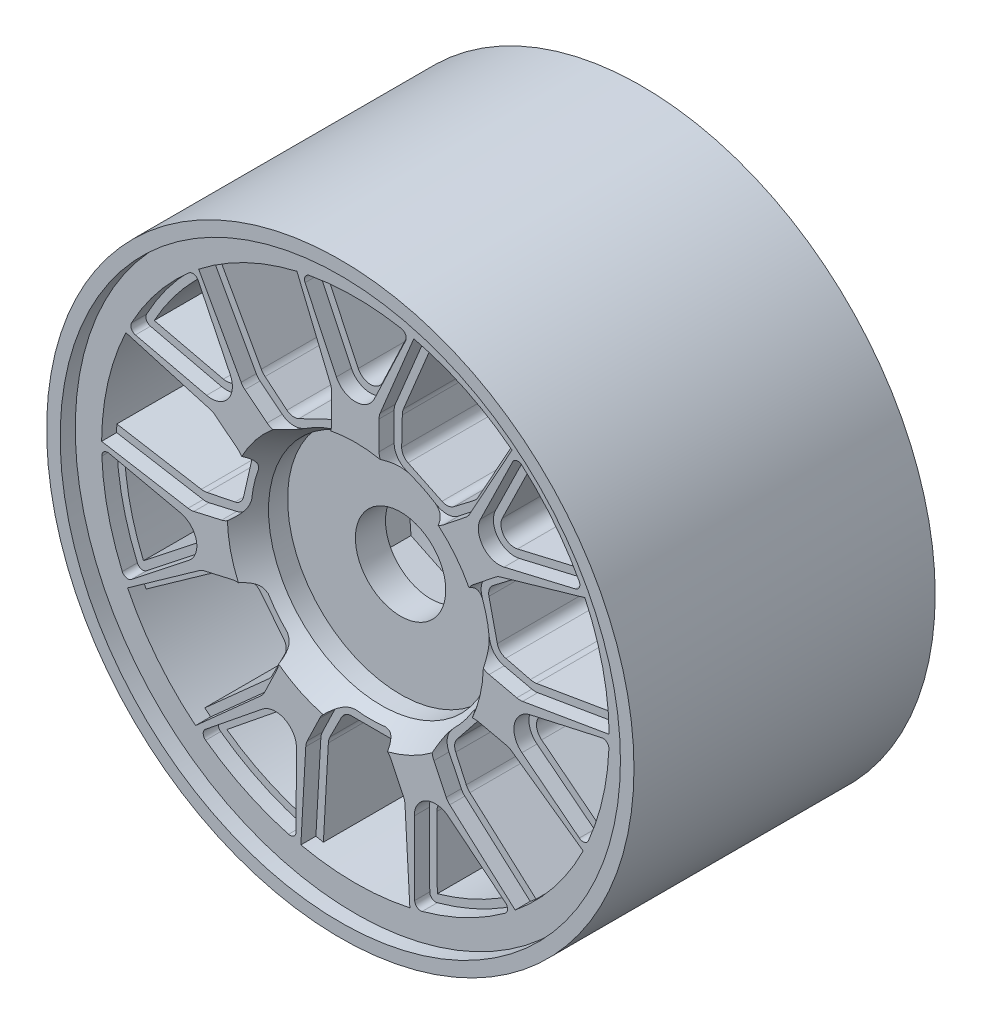
SolidWorks part; units mm, degrees
material "ABS"
ref_plane "Front Plane" through (0, 0, 0) normal (0, 0, 1) x (1, 0, 0)
ref_plane "Top Plane" through (0, 0, 0) normal (0, 1, 0) x (1, 0, 0)
ref_plane "Right Plane" through (0, 0, 0) normal (1, 0, 0) x (0, 0, -1)
sketch "Sketch1" plane through (0, 0, 0) normal (0, 0, 1) x (1, 0, 0)
  circle A0 centre (0, 0) radius 39
  dimension "D1" = 78
extrude "Boss-Extrude1" add sketch "Sketch1" along normal blind 40
sketch "Sketch2" plane through (0, 0, 0) normal (0, 0, -1) x (-1, 0, 0)
  circle A0 centre (0, 0) radius 38
  circle A1 centre (0, 0) radius 39 construction
  dimension "D1" = 1
extrude "Cut-Extrude1" cut sketch "Sketch2" against normal blind 19
sketch "Sketch3" plane through (0, 0, 40) normal (0, 0, 1) x (1, 0, 0)
  circle A0 centre (0, 0) radius 37.2
  circle A1 centre (0, 0) radius 39 construction
  dimension "D1" = 1.8
extrude "Cut-Extrude2" cut sketch "Sketch3" against normal blind 2
sketch "Sketch5" plane through (0, 0, 38) normal (0, 0, 1) x (1, 0, 0)
  circle A0 centre (0, 0) radius 6
  dimension "D1" = 12
extrude "Cut-Extrude3" cut sketch "Sketch5" against normal through all
sketch "Sketch6" plane through (0, 0, 38) normal (0, 0, 1) x (1, 0, 0)
  circle A0 centre (0, 0) radius 33.7
  circle A1 centre (0, 0) radius 37.2 construction
  dimension "D1" = 3.5
sketch "Sketch7" plane through (0, 0, 38) normal (0, 0, 1) x (1, 0, 0)
  line L0 (0, 42.1096) -> (0, -43.6902) construction
  line L1 (-45.1954, 0) -> (51.367, 0) construction
  line L2 (-3.15, 14.6655) -> (-3.15, 21.2677)
  line L3 (-3.15, 21.6655) -> (3.15, 21.6655)
  line L4 (3.15, 21.2677) -> (3.15, 14.6655)
  line L5 (-6.6789, 32.0306) -> (-2.5217, 23.2608)
  line L6 (2.5217, 23.2608) -> (6.6789, 32.0306)
  line L7 (3.3022, 22.0331) -> (7.7598, 32.7945)
  line L8 (-3.3022, 22.0331) -> (-7.7598, 32.7945)
  line L9 (1.618, 23.6891) -> (5.656, 32.2071)
  line L10 (-5.656, 32.2071) -> (-1.618, 23.6891)
  line L11 (20.8783, 25.1925) -> (16.6138, 16.4744)
  line L12 (21.6541, 24.5028) -> (17.5121, 16.035)
  line L13 (19.2851, 11.1556) -> (30.4779, 14.3802)
  line L14 (19.5297, 13.5049) -> (28.707, 15.6588)
  line L15 (19.7582, 12.5314) -> (29.2068, 14.749)
  line L16 (15.1672, 16.3192) -> (20.8016, 26.5138)
  line L17 (14.9748, 15.971) -> (18.9028, 11.0455)
  line L18 (9.502, 11.6066) -> (14.6638, 15.723)
  line L19 (18.5917, 10.7974) -> (13.43, 6.681)
  line L20 (32.7137, -0.616) -> (23.2387, -2.7176)
  line L21 (32.6582, -1.6526) -> (23.4552, -3.6939)
  line L22 (20.7458, -8.1223) -> (30.2455, -14.8627)
  line L23 (22.7352, -6.8488) -> (30.1411, -12.6809)
  line L24 (22.1165, -7.6344) -> (29.7413, -13.639)
  line L25 (22.2155, -1.6834) -> (33.6989, 0.2677)
  line L26 (21.8233, -1.75) -> (20.4214, -7.8921)
  line L27 (14.9988, -0.1924) -> (21.4354, -1.6615)
  line L28 (20.0335, -7.8035) -> (13.5969, -6.3344)
  line L29 (19.9151, -25.9607) -> (12.3644, -19.8631)
  line L30 (19.07, -26.5636) -> (11.7361, -20.6411)
  line L31 (6.5846, -21.2839) -> (7.2377, -32.9136)
  line L32 (8.8205, -22.0452) -> (8.8783, -31.4717)
  line L33 (7.8205, -22.0513) -> (7.88, -31.7564)
  line L34 (12.535, -18.4183) -> (21.2203, -26.18)
  line L35 (12.2384, -18.1532) -> (6.5623, -20.8867)
  line L36 (9.2012, -11.8464) -> (12.0658, -17.7948)
  line L37 (6.3897, -20.5283) -> (3.5251, -14.5799)
  line L38 (-7.88, -31.7564) -> (-7.8205, -22.0513)
  line L39 (-8.8783, -31.4717) -> (-8.8205, -22.0452)
  line L40 (-12.535, -18.4183) -> (-21.2203, -26.18)
  line L41 (-11.7361, -20.6411) -> (-19.07, -26.5636)
  line L42 (-12.3644, -19.8631) -> (-19.9151, -25.9607)
  line L43 (-6.5846, -21.2839) -> (-7.2377, -32.9136)
  line L44 (-6.5623, -20.8867) -> (-12.2384, -18.1532)
  line L45 (-3.5251, -14.5799) -> (-6.3897, -20.5283)
  line L46 (-12.0658, -17.7948) -> (-9.2012, -11.8464)
  line L47 (-29.7413, -13.639) -> (-22.1165, -7.6344)
  line L48 (-30.1411, -12.6809) -> (-22.7352, -6.8488)
  line L49 (-22.2155, -1.6834) -> (-33.6989, 0.2677)
  line L50 (-23.4552, -3.6939) -> (-32.6582, -1.6526)
  line L51 (-23.2387, -2.7176) -> (-32.7137, -0.616)
  line L52 (-20.7458, -8.1223) -> (-30.2455, -14.8627)
  line L53 (-20.4214, -7.8921) -> (-21.8233, -1.75)
  line L54 (-13.5969, -6.3344) -> (-20.0335, -7.8035)
  line L55 (-21.4354, -1.6615) -> (-14.9988, -0.1924)
  line L56 (-29.2068, 14.749) -> (-19.7582, 12.5314)
  line L57 (-28.707, 15.6588) -> (-19.5297, 13.5049)
  line L58 (-15.1672, 16.3192) -> (-20.8016, 26.5138)
  line L59 (-17.5121, 16.035) -> (-21.6541, 24.5028)
  line L60 (-16.6138, 16.4744) -> (-20.8783, 25.1925)
  line L61 (-19.2851, 11.1556) -> (-30.4779, 14.3802)
  line L62 (-18.9028, 11.0455) -> (-14.9748, 15.971)
  line L63 (-13.43, 6.681) -> (-18.5917, 10.7974)
  line L64 (-14.6638, 15.723) -> (-9.502, 11.6066)
  line L65 (4.5653, 15.2418) -> (9.0701, 13.0724)
  line L67 (3.15, 14.6655) -> (9.502, 11.6066) construction
  line L69 (6.326, 13.136) -> (7.7598, 16.1133) construction
  line L70 (4.9992, 16.1428) -> (9.504, 13.9734)
  line L71 (8.7397, 32.547) -> (4.3846, 22.0331)
  line L72 (4.2324, 21.2677) -> (4.15, 17.4943)
  line L73 (19.9972, 27.1257) -> (14.2999, 16.8172)
  line L74 (13.7639, 16.1956) -> (11.0901, 14.1521)
  line L75 (14.9748, 15.971) -> (13.7119, 17.5546) construction
  line L76 (14.763, 5.9338) -> (15.8756, 1.0592)
  line L77 (15.7379, 6.1564) -> (16.8505, 1.2817)
  line L78 (19.2666, 9.9512) -> (16.265, 7.6629)
  line L79 (30.8954, 13.4598) -> (19.9599, 10.3093)
  line L80 (19.2851, 11.1556) -> (30.4779, 14.3802)
  line L81 (18.5917, 10.7974) -> (13.43, 6.681)
  line L82 (21.2439, -0.6633) -> (17.9791, 0.1531)
  line L83 (14.9988, -0.1924) -> (21.4354, -1.6615)
  line L84 (33.6758, 1.2781) -> (22.0641, -0.6948)
  line L85 (22.2155, -1.6834) -> (33.6989, 0.2677)
  line L86 (13.43, 6.681) -> (14.9988, -0.1924) construction
  line L87 (14.2144, 3.2443) -> (17.436, 3.9797) construction
  line L88 (13.8438, -7.8425) -> (10.7264, -11.7516)
  line L89 (14.6256, -8.4659) -> (11.5082, -12.3751)
  line L90 (19.7927, -8.8588) -> (16.1322, -7.9388)
  line L91 (29.7862, -15.7629) -> (20.505, -9.1775)
  line L92 (20.7458, -8.1223) -> (30.2455, -14.8627)
  line L93 (20.0335, -7.8035) -> (13.5969, -6.3344)
  line L94 (12.7268, -17.0227) -> (11.3295, -13.9612)
  line L95 (9.2012, -11.8464) -> (12.0658, -17.7948)
  line L96 (21.9958, -25.5319) -> (13.2136, -17.6836)
  line L97 (12.535, -18.4183) -> (21.2203, -26.18)
  line L98 (13.5969, -6.3344) -> (9.2012, -11.8464) construction
  line L99 (11.399, -9.0904) -> (13.9826, -11.1507) construction
  line L100 (2.5, -15.7132) -> (-2.5, -15.7132)
  line L101 (2.5, -16.7132) -> (-2.5, -16.7132)
  line L102 (5.4145, -20.9979) -> (3.8515, -17.5624)
  line L103 (6.2475, -33.1158) -> (5.6094, -21.7535)
  line L104 (6.5846, -21.2839) -> (7.2377, -32.9136)
  line L105 (6.3897, -20.5283) -> (3.5251, -14.5799)
  line L106 (-5.3739, -20.5637) -> (-3.8515, -17.5624)
  line L107 (-3.5251, -14.5799) -> (-6.3897, -20.5283)
  line L108 (-6.2475, -33.1158) -> (-5.5871, -21.3563)
  line L109 (-6.5846, -21.2839) -> (-7.2377, -32.9136)
  line L110 (3.5251, -14.5799) -> (-3.5251, -14.5799) construction
  line L111 (0, -14.5799) -> (0, -17.8844) construction
  line L112 (-10.7264, -11.7516) -> (-13.8438, -7.8425)
  line L113 (-11.5082, -12.3751) -> (-14.6256, -8.4659)
  line L114 (-13.041, -17.3252) -> (-11.3295, -13.9612)
  line L115 (-21.9958, -25.5319) -> (-13.5102, -17.9487)
  line L116 (-12.535, -18.4183) -> (-21.2203, -26.18)
  line L117 (-12.0658, -17.7948) -> (-9.2012, -11.8464)
  line L118 (-19.4279, -8.6198) -> (-16.1322, -7.9388)
  line L119 (-13.5969, -6.3344) -> (-20.0335, -7.8035)
  line L120 (-29.7862, -15.7629) -> (-20.1805, -8.9473)
  line L121 (-20.7458, -8.1223) -> (-30.2455, -14.8627)
  line L122 (-9.2012, -11.8464) -> (-13.5969, -6.3344) construction
  line L123 (-11.399, -9.0904) -> (-13.9826, -11.1507) construction
  line L124 (-15.8756, 1.0592) -> (-14.763, 5.9338)
  line L125 (-16.8505, 1.2817) -> (-15.7379, 6.1564)
  line L126 (-21.6763, -0.6062) -> (-17.9791, 0.1531)
  line L127 (-33.6758, 1.2781) -> (-22.4563, -0.6281)
  line L128 (-22.2155, -1.6834) -> (-33.6989, 0.2677)
  line L129 (-21.4354, -1.6615) -> (-14.9988, -0.1924)
  line L130 (-18.8523, 9.815) -> (-16.265, 7.6629)
  line L131 (-13.43, 6.681) -> (-18.5917, 10.7974)
  line L132 (-30.8954, 13.4598) -> (-19.5776, 10.1992)
  line L133 (-19.2851, 11.1556) -> (-30.4779, 14.3802)
  line L134 (-14.9988, -0.1924) -> (-13.43, 6.681) construction
  line L135 (-14.2144, 3.2443) -> (-17.436, 3.9797) construction
  line L136 (-9.0701, 13.0724) -> (-4.5653, 15.2418)
  line L137 (-9.504, 13.9734) -> (-4.9992, 16.1428)
  line L138 (-13.9889, 16.5692) -> (-11.0901, 14.1521)
  line L139 (-19.9972, 27.1257) -> (-14.4924, 17.1654)
  line L140 (-15.1672, 16.3192) -> (-20.8016, 26.5138)
  line L141 (-14.6638, 15.723) -> (-9.502, 11.6066)
  line L142 (-4.0806, 20.8589) -> (-4.15, 17.4943)
  line L143 (-3.15, 14.6655) -> (-3.15, 21.2677)
  line L144 (-8.7397, 32.547) -> (-4.2324, 21.6655)
  line L145 (-3.3022, 22.0331) -> (-7.7598, 32.7945)
  line L146 (-9.502, 11.6066) -> (-3.15, 14.6655) construction
  line L147 (-6.326, 13.136) -> (-7.7598, 16.1133) construction
  circle A0 centre (0, 0) radius 15
  circle A1 centre (0, 0) radius 33.7 construction
  arc A2 (-6.1106, 33.1414) -> (6.1106, 33.1414) centre (0, 0) cw
  arc A3 (-6.1106, 33.1414) -> (-6.6789, 32.0306) centre (-5.968, 32.3676) ccw
  arc A4 (6.1106, 33.1414) -> (6.6789, 32.0306) centre (5.968, 32.3676) cw
  arc A5 (-2.5217, 23.2608) -> (2.5217, 23.2608) centre (0, 24.4562) ccw
  arc A6 (-33.7, 0) -> (33.7, 0) centre (0, 0) ccw
  arc A7 (7.7598, 32.7945) -> (-7.7598, 32.7945) centre (0, 0) ccw
  arc A8 (-5.656, 32.2071) -> (5.656, 32.2071) centre (0, 0) cw
  arc A9 (5.656, 32.2071) -> (5.656, 32.2071) centre (5.656, 32.2071) cw
  arc A10 (-1.618, 23.6891) -> (1.618, 23.6891) centre (0, 24.4562) ccw
  arc A11 (-5.656, 32.2071) -> (-5.656, 32.2071) centre (-5.656, 32.2071) ccw
  arc A12 (21.6541, 24.5028) -> (28.707, 15.6588) centre (0, 0) cw
  arc A13 (22.101, 25.4408) -> (29.7209, 15.8858) centre (0, 0) cw
  arc A14 (22.101, 25.4408) -> (20.8783, 25.1925) centre (21.5851, 24.8468) ccw
  arc A15 (30.4779, 14.3802) -> (20.8016, 26.5138) centre (0, 0) ccw
  arc A16 (29.7209, 15.8858) -> (29.2068, 14.749) centre (29.027, 15.5149) cw
  arc A17 (16.6138, 16.4744) -> (19.7582, 12.5314) centre (19.1206, 15.2482) ccw
  arc A18 (17.5121, 16.035) -> (19.5297, 13.5049) centre (19.1206, 15.2482) ccw
  arc A19 (32.6582, -1.6526) -> (30.1411, -12.6809) centre (0, 0) cw
  arc A20 (33.6702, -1.4172) -> (30.9507, -13.3321) centre (0, 0) cw
  arc A21 (33.6702, -1.4172) -> (32.7137, -0.616) centre (32.8841, -1.3841) ccw
  arc A22 (30.2455, -14.8627) -> (33.6989, 0.2677) centre (0, 0) ccw
  arc A23 (30.9507, -13.3321) -> (29.7413, -13.639) centre (30.2281, -13.0208) cw
  arc A24 (23.2387, -2.7176) -> (22.1165, -7.6344) centre (23.843, -5.442) ccw
  arc A25 (23.4552, -3.6939) -> (22.7352, -6.8488) centre (23.843, -5.442) ccw
  arc A26 (19.07, -26.5636) -> (8.8783, -31.4717) centre (0, 0) cw
  arc A27 (19.885, -27.208) -> (8.874, -32.5106) centre (0, 0) cw
  arc A28 (19.885, -27.208) -> (19.9151, -25.9607) centre (19.4207, -26.5728) ccw
  arc A29 (7.2377, -32.9136) -> (21.2203, -26.18) centre (0, 0) ccw
  arc A30 (8.874, -32.5106) -> (7.88, -31.7564) centre (8.6668, -31.7516) cw
  arc A31 (12.3644, -19.8631) -> (7.8205, -22.0513) centre (10.6111, -22.0342) ccw
  arc A32 (11.7361, -20.6411) -> (8.8205, -22.0452) centre (10.6111, -22.0342) ccw
  arc A33 (-8.8783, -31.4717) -> (-19.07, -26.5636) centre (0, 0) cw
  arc A34 (-8.874, -32.5106) -> (-19.885, -27.208) centre (0, 0) cw
  arc A35 (-8.874, -32.5106) -> (-7.88, -31.7564) centre (-8.6668, -31.7516) ccw
  arc A36 (-21.2203, -26.18) -> (-7.2377, -32.9136) centre (0, 0) ccw
  arc A37 (-19.885, -27.208) -> (-19.9151, -25.9607) centre (-19.4207, -26.5728) cw
  arc A38 (-7.8205, -22.0513) -> (-12.3644, -19.8631) centre (-10.6111, -22.0342) ccw
  arc A39 (-8.8205, -22.0452) -> (-11.7361, -20.6411) centre (-10.6111, -22.0342) ccw
  arc A40 (-30.1411, -12.6809) -> (-32.6582, -1.6526) centre (0, 0) cw
  arc A41 (-30.9507, -13.3321) -> (-33.6702, -1.4172) centre (0, 0) cw
  arc A42 (-30.9507, -13.3321) -> (-29.7413, -13.639) centre (-30.2281, -13.0208) ccw
  arc A43 (-33.6989, 0.2677) -> (-30.2455, -14.8627) centre (0, 0) ccw
  arc A44 (-33.6702, -1.4172) -> (-32.7137, -0.616) centre (-32.8841, -1.3841) cw
  arc A45 (-22.1165, -7.6344) -> (-23.2387, -2.7176) centre (-23.843, -5.442) ccw
  arc A46 (-22.7352, -6.8488) -> (-23.4552, -3.6939) centre (-23.843, -5.442) ccw
  arc A47 (-28.707, 15.6588) -> (-21.6541, 24.5028) centre (0, 0) cw
  arc A48 (-29.7209, 15.8858) -> (-22.101, 25.4408) centre (0, 0) cw
  arc A49 (-29.7209, 15.8858) -> (-29.2068, 14.749) centre (-29.027, 15.5149) ccw
  arc A50 (-20.8016, 26.5138) -> (-30.4779, 14.3802) centre (0, 0) ccw
  arc A51 (-22.101, 25.4408) -> (-20.8783, 25.1925) centre (-21.5851, 24.8468) cw
  arc A52 (-19.7582, 12.5314) -> (-16.6138, 16.4744) centre (-19.1206, 15.2482) ccw
  arc A53 (-19.5297, 13.5049) -> (-17.5121, 16.035) centre (-19.1206, 15.2482) ccw
  arc A55 (3.15, 21.2677) -> (3.3022, 22.0331) centre (5.15, 21.2677) cw
  arc A56 (-3.15, 21.2677) -> (-3.3022, 22.0331) centre (-5.15, 21.2677) ccw
  arc A57 (-14.6638, 15.723) -> (-15.1672, 16.3192) centre (-13.4168, 17.2866) cw
  arc A58 (-18.5917, 10.7974) -> (-19.2851, 11.1556) centre (-19.8387, 9.2338) ccw
  arc A59 (-21.4354, -1.6615) -> (-22.2155, -1.6834) centre (-21.8805, 0.2884) cw
  arc A60 (-20.7458, -8.1223) -> (-20.0335, -7.8035) centre (-19.5885, -9.7534) cw
  arc A61 (-12.0658, -17.7948) -> (-12.535, -18.4183) centre (-13.8677, -16.927) cw
  arc A62 (-6.3897, -20.5283) -> (-6.5846, -21.2839) centre (-4.5877, -21.396) ccw
  arc A63 (12.0658, -17.7948) -> (12.535, -18.4183) centre (13.8677, -16.927) ccw
  arc A64 (6.3897, -20.5283) -> (6.5846, -21.2839) centre (4.5877, -21.396) cw
  arc A65 (20.0335, -7.8035) -> (20.7458, -8.1223) centre (19.5885, -9.7534) cw
  arc A66 (22.2155, -1.6834) -> (21.4354, -1.6615) centre (21.8805, 0.2884) cw
  arc A67 (19.2851, 11.1556) -> (18.5917, 10.7974) centre (19.8387, 9.2338) ccw
  arc A68 (15.1672, 16.3192) -> (14.6638, 15.723) centre (13.4168, 17.2866) cw
  arc A69 (4.5653, 15.2418) -> (3.15, 17.4943) centre (5.65, 17.4943) cw
  arc A70 (9.0701, 13.0724) -> (11.7136, 13.3703) centre (10.1548, 15.3248) ccw
  arc A71 (4.9992, 16.1428) -> (4.15, 17.4943) centre (5.65, 17.4943) cw
  arc A72 (9.504, 13.9734) -> (11.0901, 14.1521) centre (10.1548, 15.3248) ccw
  arc A73 (4.3846, 22.0331) -> (4.2324, 21.2677) centre (6.2324, 21.2677) ccw
  arc A74 (14.2999, 16.8172) -> (13.7639, 16.1956) centre (12.5495, 17.7847) cw
  arc A75 (8.7397, 32.547) -> (19.9972, 27.1257) centre (0, 0) cw
  arc A76 (14.763, 5.9338) -> (15.6416, 8.4447) centre (17.2003, 6.4901) cw
  arc A77 (15.7379, 6.1564) -> (16.265, 7.6629) centre (17.2003, 6.4901) cw
  arc A78 (19.9599, 10.3093) -> (19.2666, 9.9512) centre (20.5136, 8.3875) ccw
  arc A79 (18.5917, 10.7974) -> (19.2851, 11.1556) centre (19.8387, 9.2338) cw
  arc A80 (15.8756, 1.0592) -> (17.7566, -0.8218) centre (18.3129, 1.6155) ccw
  arc A81 (16.8505, 1.2817) -> (17.9791, 0.1531) centre (18.3129, 1.6155) ccw
  arc A82 (22.0641, -0.6948) -> (21.2439, -0.6633) centre (21.7291, 1.277) cw
  arc A83 (22.2155, -1.6834) -> (21.4354, -1.6615) centre (21.8805, 0.2884) cw
  arc A84 (30.8954, 13.4598) -> (33.6758, 1.2781) centre (0, 0) cw
  arc A85 (13.8438, -7.8425) -> (16.3547, -6.9639) centre (15.7984, -9.4012) cw
  arc A86 (14.6256, -8.4659) -> (16.1322, -7.9388) centre (15.7984, -9.4012) cw
  arc A87 (20.505, -9.1775) -> (19.7927, -8.8588) centre (19.3476, -10.8086) ccw
  arc A88 (20.0335, -7.8035) -> (20.7458, -8.1223) centre (19.5885, -9.7534) cw
  arc A89 (10.7264, -11.7516) -> (10.4285, -14.395) centre (12.6809, -13.3103) ccw
  arc A90 (11.5082, -12.3751) -> (11.3295, -13.9612) centre (12.6809, -13.3103) ccw
  arc A91 (13.2136, -17.6836) -> (12.7268, -17.0227) centre (14.5463, -16.1923) cw
  arc A92 (12.535, -18.4183) -> (12.0658, -17.7948) centre (13.8677, -16.927) cw
  arc A93 (29.7862, -15.7629) -> (21.9958, -25.5319) centre (0, 0) cw
  arc A94 (2.5, -15.7132) -> (4.7524, -17.1285) centre (2.5, -18.2132) cw
  arc A95 (2.5, -16.7132) -> (3.8515, -17.5624) centre (2.5, -18.2132) cw
  arc A96 (5.6094, -21.7535) -> (5.4145, -20.9979) centre (3.6125, -21.8657) ccw
  arc A97 (6.3897, -20.5283) -> (6.5846, -21.2839) centre (4.5877, -21.396) cw
  arc A98 (-2.5, -15.7132) -> (-4.7524, -17.1285) centre (-2.5, -18.2132) ccw
  arc A99 (-2.5, -16.7132) -> (-3.8515, -17.5624) centre (-2.5, -18.2132) ccw
  arc A100 (-5.5871, -21.3563) -> (-5.3739, -20.5637) centre (-3.5902, -21.4685) cw
  arc A101 (-6.5846, -21.2839) -> (-6.3897, -20.5283) centre (-4.5877, -21.396) cw
  arc A102 (6.2475, -33.1158) -> (-6.2475, -33.1158) centre (0, 0) cw
  arc A103 (-10.7264, -11.7516) -> (-10.4285, -14.395) centre (-12.6809, -13.3103) cw
  arc A104 (-11.5082, -12.3751) -> (-11.3295, -13.9612) centre (-12.6809, -13.3103) cw
  arc A105 (-13.5102, -17.9487) -> (-13.041, -17.3252) centre (-14.8429, -16.4574) ccw
  arc A106 (-12.0658, -17.7948) -> (-12.535, -18.4183) centre (-13.8677, -16.927) cw
  arc A107 (-13.8438, -7.8425) -> (-16.3547, -6.9639) centre (-15.7984, -9.4012) ccw
  arc A108 (-14.6256, -8.4659) -> (-16.1322, -7.9388) centre (-15.7984, -9.4012) ccw
  arc A109 (-20.1805, -8.9473) -> (-19.4279, -8.6198) centre (-19.0232, -10.5784) cw
  arc A110 (-20.7458, -8.1223) -> (-20.0335, -7.8035) centre (-19.5885, -9.7534) cw
  arc A111 (-21.9958, -25.5319) -> (-29.7862, -15.7629) centre (0, 0) cw
  arc A112 (-15.8756, 1.0592) -> (-17.7566, -0.8218) centre (-18.3129, 1.6155) cw
  arc A113 (-16.8505, 1.2817) -> (-17.9791, 0.1531) centre (-18.3129, 1.6155) cw
  arc A114 (-22.4563, -0.6281) -> (-21.6763, -0.6062) centre (-22.1213, 1.3436) ccw
  arc A115 (-21.4354, -1.6615) -> (-22.2155, -1.6834) centre (-21.8805, 0.2884) cw
  arc A116 (-14.763, 5.9338) -> (-15.6416, 8.4447) centre (-17.2003, 6.4901) ccw
  arc A117 (-15.7379, 6.1564) -> (-16.265, 7.6629) centre (-17.2003, 6.4901) ccw
  arc A118 (-19.5776, 10.1992) -> (-18.8523, 9.815) centre (-20.1313, 8.2774) cw
  arc A119 (-19.2851, 11.1556) -> (-18.5917, 10.7974) centre (-19.8387, 9.2338) cw
  arc A120 (-33.6758, 1.2781) -> (-30.8954, 13.4598) centre (0, 0) cw
  arc A121 (-9.0701, 13.0724) -> (-11.7136, 13.3703) centre (-10.1548, 15.3248) cw
  arc A122 (-9.504, 13.9734) -> (-11.0901, 14.1521) centre (-10.1548, 15.3248) cw
  arc A123 (-14.4924, 17.1654) -> (-13.9889, 16.5692) centre (-12.7419, 18.1329) ccw
  arc A124 (-14.6638, 15.723) -> (-15.1672, 16.3192) centre (-13.4168, 17.2866) cw
  arc A125 (-4.5653, 15.2418) -> (-3.15, 17.4943) centre (-5.65, 17.4943) ccw
  arc A126 (-4.9992, 16.1428) -> (-4.15, 17.4943) centre (-5.65, 17.4943) ccw
  arc A127 (-4.2324, 21.6655) -> (-4.0806, 20.8589) centre (-6.0802, 20.9002) cw
  arc A128 (-3.3022, 22.0331) -> (-3.15, 21.2677) centre (-5.15, 21.2677) cw
  arc A129 (-19.9972, 27.1257) -> (-8.7397, 32.547) centre (0, 0) cw
  circle A130 centre (0, 0) radius 33.7
  point P24 (-2.5217, 23.2608)
  point P25 (2.5217, 23.2608)
  point P173 (0, 0)
  point P210 (6.8177, 14.1571)
  point P421 (0, 0)
  dimension "D1" = 30
  dimension "D8" = 0.7868
  dimension "D9" = 22.5
  dimension "D4" = 9.7053
  dimension "D7" = 0.7868
  dimension "D11" = 2.7906
  dimension "D14" = 2.5
  dimension "D15" = 2
  dimension "D16" = 2
  dimension "D17" = 2
  dimension "D18" = 2
  dimension "D19" = 2
  dimension "D20" = 2
  dimension "D21" = 2
  dimension "D22" = 2
  dimension "D23" = 2
  dimension "D24" = 2
  dimension "D25" = 2
  dimension "D26" = 2
  dimension "D27" = 2
  dimension "D28" = 2
  dimension "D29" = 7.0502
  dimension "D33" = 2
  dimension "D35" = 2
  dimension "D36" = 33.7
  dimension "D38" = 67.4
  dimension "D2" = 6.3
  dimension "D3" = 7
  dimension "D5" = 25.363
  dimension "D6" = 9.7053
  dimension "D10" = 22.5
  dimension "D30" = 5
  dimension "D32" = 1
  dimension "D34" = 1
  dimension "D12" = 1
  dimension "D31" = 1
  dimension "D13" = 7
  dimension "D37" = 7
extrude "Cut-Extrude5" cut sketch "Sketch7" against normal blind 2 contours L10 A10 L9 A8 | L5 A5 L6 A4 A2 A3 A10 L10 A8 L9 | L8 A130 L144 A127 L142 A126 L137 A122 L138 A123 L139 L58 A57 L64 A121 L136 A125 L143 A56 | A129 L139 A123 L138 A122 L137 A126 L142 A127 L144 | L56 A52 L60 A51 A48 A49 A53 L57 A47 L59 | L57 A53 L59 A47 | L61 A130 L132 A118 L130 A117 L125 A113 L126 A114 L127 L49 A59 L55 A112 L124 A116 L131 A58 | A120 L127 A114 L126 A113 L125 A117 L130 A118 L132 | A45 L51 A44 A6 A42 L47 A46 L48 A40 L50 | L48 A46 L50 A40 | L120 A109 L118 A108 L113 A104 L114 A105 L115 A6 L40 A61 L46 A103 L112 A107 L119 A60 L52 | A109 L120 A6 L115 A105 L114 A104 L113 A108 L118 | A38 L42 A37 A6 A35 L38 A39 L39 A33 L41 | L39 A39 L41 A33 | L108 A100 L106 A99 L101 A95 L102 A96 L103 A6 L31 A64 L37 A94 L100 A98 L107 A62 L43 | A100 L108 A6 L103 A96 L102 A95 L101 A99 L106 | L29 A31 L33 A30 A6 A28 A32 L30 A26 L32 | L30 A32 L32 A26 | L96 A91 L94 A90 L89 A86 L90 A87 L91 A6 L22 A65 L28 A85 L88 A89 L95 A63 L34 | A91 L96 A6 L91 A87 L90 A86 L89 A90 L94 | L20 A24 L24 A23 A6 A21 A25 L21 A19 L23 | L21 A25 L23 A19 | L25 A130 L84 A82 L82 A81 L77 A77 L78 A78 L79 L13 A67 L19 A76 L76 A80 L83 A66 | A84 L79 A78 L78 A77 L77 A81 L82 A82 L84 | A75 L71 A73 L72 A71 L70 A72 L74 A74 L73 | L16 A130 L73 A74 L74 A72 L70 A71 L72 A73 L71 L7 A55 L4 A69 L65 A70 L18 A68 | L11 A17 L15 A16 A13 A14 A18 L12 A12 L14 | L12 A18 L14 A12 region at (-3.7589, 16.306, 38) region at (3.4165, 19.381, 38) region at (-15.0756, 7.2336, 38) region at (17.2719, 9.4264, 38) region at (0, 33.5191, 38) region at (-11.1311, 23.1347, 38) region at (-15.0646, -7.3041, 38) region at (11.1473, 23.1269, 38) region at (-21.466, 25.4331, 38) region at (26.2003, 20.8941, 38) region at (18.1322, -7.655, 38) region at (-25.0276, 5.7216, 38) region at (-3.7096, -16.2881, 38) region at (25.0316, 5.7041, 38) region at (-33.272, -0.921, 38) region at (-20.0777, -16, 38) region at (-20.0256, -26.5874, 38) region at (32.677, -7.4583, 38) region at (20.0666, -16.014, 38) region at (-0.009, -25.6733, 38) region at (14.543, -30.1989, 38) region at (0, 28.7459, 38) region at (22.4745, 17.9228, 38) region at (28.0252, -6.3966, 38) region at (12.4724, -25.8992, 38) region at (-12.4724, -25.8992, 38) region at (-28.0252, -6.3966, 38) region at (-22.4745, 17.9228, 38)
sketch "Sketch8" plane through (0, 0, 38) normal (0, 0, 1) x (1, 0, 0)
  circle A0 centre (0, 0) radius 15 construction
  circle A1 centre (0, 0) radius 15
extrude "Cut-Extrude6" cut sketch "Sketch8" against normal blind 6
sketch "Sketch9" plane through (0, 0, 38) normal (0, 0, 1) x (1, 0, 0)
  line L0 (-33.6758, 1.2781) -> (-22.4563, -0.6281) construction
  line L1 (-21.6763, -0.6062) -> (-17.9791, 0.1531) construction
  line L2 (-16.8505, 1.2817) -> (-15.7379, 6.1564) construction
  line L3 (-18.8523, 9.815) -> (-16.265, 7.6629) construction
  line L4 (-30.8954, 13.4598) -> (-19.5776, 10.1992) construction
  line L5 (-23.4552, -3.6939) -> (-32.6582, -1.6526) construction
  line L6 (-30.1411, -12.6809) -> (-22.7352, -6.8488) construction
  line L7 (-29.7862, -15.7629) -> (-20.1805, -8.9473) construction
  line L8 (-19.4279, -8.6198) -> (-16.1322, -7.9388) construction
  line L9 (-11.5082, -12.3751) -> (-14.6256, -8.4659) construction
  line L10 (-13.041, -17.3252) -> (-11.3295, -13.9612) construction
  line L11 (-21.9958, -25.5319) -> (-13.5102, -17.9487) construction
  line L12 (-11.7361, -20.6411) -> (-19.07, -26.5636) construction
  line L13 (-8.8783, -31.4717) -> (-8.8205, -22.0452) construction
  line L14 (-6.2475, -33.1158) -> (-5.5871, -21.3563) construction
  line L15 (-5.3739, -20.5637) -> (-3.8515, -17.5624) construction
  line L16 (2.5, -16.7132) -> (-2.5, -16.7132) construction
  line L17 (5.4145, -20.9979) -> (3.8515, -17.5624) construction
  line L18 (6.2475, -33.1158) -> (5.6094, -21.7535) construction
  line L19 (8.8205, -22.0452) -> (8.8783, -31.4717) construction
  line L20 (19.07, -26.5636) -> (11.7361, -20.6411) construction
  line L21 (21.9958, -25.5319) -> (13.2136, -17.6836) construction
  line L22 (12.7268, -17.0227) -> (11.3295, -13.9612) construction
  line L23 (14.6256, -8.4659) -> (11.5082, -12.3751) construction
  line L24 (19.7927, -8.8588) -> (16.1322, -7.9388) construction
  line L25 (29.7862, -15.7629) -> (20.505, -9.1775) construction
  line L26 (22.7352, -6.8488) -> (30.1411, -12.6809) construction
  line L27 (32.6582, -1.6526) -> (23.4552, -3.6939) construction
  line L28 (33.6758, 1.2781) -> (22.0641, -0.6948) construction
  line L29 (21.2439, -0.6633) -> (17.9791, 0.1531) construction
  line L30 (15.7379, 6.1564) -> (16.8505, 1.2817) construction
  line L31 (19.2666, 9.9512) -> (16.265, 7.6629) construction
  line L32 (30.8954, 13.4598) -> (19.9599, 10.3093) construction
  line L33 (19.5297, 13.5049) -> (28.707, 15.6588) construction
  line L34 (21.6541, 24.5028) -> (17.5121, 16.035) construction
  line L35 (19.9972, 27.1257) -> (14.2999, 16.8172) construction
  line L36 (13.7639, 16.1956) -> (11.0901, 14.1521) construction
  line L37 (4.9992, 16.1428) -> (9.504, 13.9734) construction
  line L38 (4.2324, 21.2677) -> (4.15, 17.4943) construction
  line L39 (8.7397, 32.547) -> (4.3846, 22.0331) construction
  line L40 (1.618, 23.6891) -> (5.656, 32.2071) construction
  line L41 (-5.656, 32.2071) -> (-1.618, 23.6891) construction
  line L42 (-28.707, 15.6588) -> (-19.5297, 13.5049) construction
  line L43 (-17.5121, 16.035) -> (-21.6541, 24.5028) construction
  line L44 (-8.7397, 32.547) -> (-4.2324, 21.6655) construction
  line L45 (-4.0806, 20.8589) -> (-4.15, 17.4943) construction
  line L46 (-9.504, 13.9734) -> (-4.9992, 16.1428) construction
  line L47 (-13.9889, 16.5692) -> (-11.0901, 14.1521) construction
  line L48 (-19.9972, 27.1257) -> (-14.4924, 17.1654) construction
  line L49 (-33.6758, 1.2781) -> (-22.4563, -0.6281)
  line L50 (-21.6763, -0.6062) -> (-17.9791, 0.1531)
  line L51 (-16.8505, 1.2817) -> (-15.7379, 6.1564)
  line L52 (-18.8523, 9.815) -> (-16.265, 7.6629)
  line L53 (-30.8954, 13.4598) -> (-19.5776, 10.1992)
  line L54 (-23.4552, -3.6939) -> (-32.6582, -1.6526)
  line L55 (-30.1411, -12.6809) -> (-22.7352, -6.8488)
  line L56 (-29.7862, -15.7629) -> (-20.1805, -8.9473)
  line L57 (-19.4279, -8.6198) -> (-16.1322, -7.9388)
  line L58 (-11.5082, -12.3751) -> (-14.6256, -8.4659)
  line L59 (-13.041, -17.3252) -> (-11.3295, -13.9612)
  line L60 (-21.9958, -25.5319) -> (-13.5102, -17.9487)
  line L61 (-11.7361, -20.6411) -> (-19.07, -26.5636)
  line L62 (-8.8783, -31.4717) -> (-8.8205, -22.0452)
  line L63 (-6.2475, -33.1158) -> (-5.5871, -21.3563)
  line L64 (-5.3739, -20.5637) -> (-3.8515, -17.5624)
  line L65 (2.5, -16.7132) -> (-2.5, -16.7132)
  line L66 (5.4145, -20.9979) -> (3.8515, -17.5624)
  line L67 (6.2475, -33.1158) -> (5.6094, -21.7535)
  line L68 (8.8205, -22.0452) -> (8.8783, -31.4717)
  line L69 (19.07, -26.5636) -> (11.7361, -20.6411)
  line L70 (21.9958, -25.5319) -> (13.2136, -17.6836)
  line L71 (12.7268, -17.0227) -> (11.3295, -13.9612)
  line L72 (14.6256, -8.4659) -> (11.5082, -12.3751)
  line L73 (19.7927, -8.8588) -> (16.1322, -7.9388)
  line L74 (29.7862, -15.7629) -> (20.505, -9.1775)
  line L75 (22.7352, -6.8488) -> (30.1411, -12.6809)
  line L76 (32.6582, -1.6526) -> (23.4552, -3.6939)
  line L77 (33.6758, 1.2781) -> (22.0641, -0.6948)
  line L78 (21.2439, -0.6633) -> (17.9791, 0.1531)
  line L79 (15.7379, 6.1564) -> (16.8505, 1.2817)
  line L80 (19.2666, 9.9512) -> (16.265, 7.6629)
  line L81 (30.8954, 13.4598) -> (19.9599, 10.3093)
  line L82 (19.5297, 13.5049) -> (28.707, 15.6588)
  line L83 (21.6541, 24.5028) -> (17.5121, 16.035)
  line L84 (19.9972, 27.1257) -> (14.2999, 16.8172)
  line L85 (13.7639, 16.1956) -> (11.0901, 14.1521)
  line L86 (4.9992, 16.1428) -> (9.504, 13.9734)
  line L87 (4.2324, 21.2677) -> (4.15, 17.4943)
  line L88 (8.7397, 32.547) -> (4.3846, 22.0331)
  line L89 (1.618, 23.6891) -> (5.656, 32.2071)
  line L90 (-5.656, 32.2071) -> (-1.618, 23.6891)
  line L91 (-28.707, 15.6588) -> (-19.5297, 13.5049)
  line L92 (-17.5121, 16.035) -> (-21.6541, 24.5028)
  line L93 (-8.7397, 32.547) -> (-4.2324, 21.6655)
  line L94 (-4.0806, 20.8589) -> (-4.15, 17.4943)
  line L95 (-9.504, 13.9734) -> (-4.9992, 16.1428)
  line L96 (-13.9889, 16.5692) -> (-11.0901, 14.1521)
  line L97 (-19.9972, 27.1257) -> (-14.4924, 17.1654)
  arc A0 (-22.4563, -0.6281) -> (-21.6763, -0.6062) centre (-22.1213, 1.3436) ccw construction
  arc A1 (-17.9791, 0.1531) -> (-16.8505, 1.2817) centre (-18.3129, 1.6155) ccw construction
  arc A2 (-15.7379, 6.1564) -> (-16.265, 7.6629) centre (-17.2003, 6.4901) ccw construction
  arc A3 (-18.8523, 9.815) -> (-19.5776, 10.1992) centre (-20.1313, 8.2774) ccw construction
  arc A4 (-32.6582, -1.6526) -> (-30.1411, -12.6809) centre (0, 0) ccw construction
  arc A5 (-22.7352, -6.8488) -> (-23.4552, -3.6939) centre (-23.843, -5.442) ccw construction
  arc A6 (-19.4279, -8.6198) -> (-20.1805, -8.9473) centre (-19.0232, -10.5784) ccw construction
  arc A7 (-14.6256, -8.4659) -> (-16.1322, -7.9388) centre (-15.7984, -9.4012) ccw construction
  arc A8 (-11.3295, -13.9612) -> (-11.5082, -12.3751) centre (-12.6809, -13.3103) ccw construction
  arc A9 (-13.5102, -17.9487) -> (-13.041, -17.3252) centre (-14.8429, -16.4574) ccw construction
  arc A10 (-19.07, -26.5636) -> (-8.8783, -31.4717) centre (0, 0) ccw construction
  arc A11 (-8.8205, -22.0452) -> (-11.7361, -20.6411) centre (-10.6111, -22.0342) ccw construction
  arc A12 (-5.3739, -20.5637) -> (-5.5871, -21.3563) centre (-3.5902, -21.4685) ccw construction
  arc A13 (-2.5, -16.7132) -> (-3.8515, -17.5624) centre (-2.5, -18.2132) ccw construction
  arc A14 (3.8515, -17.5624) -> (2.5, -16.7132) centre (2.5, -18.2132) ccw construction
  arc A15 (5.6094, -21.7535) -> (5.4145, -20.9979) centre (3.6125, -21.8657) ccw construction
  arc A16 (11.7361, -20.6411) -> (8.8205, -22.0452) centre (10.6111, -22.0342) ccw construction
  arc A17 (8.8783, -31.4717) -> (19.07, -26.5636) centre (0, 0) ccw construction
  arc A18 (12.7268, -17.0227) -> (13.2136, -17.6836) centre (14.5463, -16.1923) ccw construction
  arc A19 (11.5082, -12.3751) -> (11.3295, -13.9612) centre (12.6809, -13.3103) ccw construction
  arc A20 (16.1322, -7.9388) -> (14.6256, -8.4659) centre (15.7984, -9.4012) ccw construction
  arc A21 (20.505, -9.1775) -> (19.7927, -8.8588) centre (19.3476, -10.8086) ccw construction
  arc A22 (23.4552, -3.6939) -> (22.7352, -6.8488) centre (23.843, -5.442) ccw construction
  arc A23 (30.1411, -12.6809) -> (32.6582, -1.6526) centre (0, 0) ccw construction
  arc A24 (21.2439, -0.6633) -> (22.0641, -0.6948) centre (21.7291, 1.277) ccw construction
  arc A25 (16.8505, 1.2817) -> (17.9791, 0.1531) centre (18.3129, 1.6155) ccw construction
  arc A26 (16.265, 7.6629) -> (15.7379, 6.1564) centre (17.2003, 6.4901) ccw construction
  arc A27 (19.9599, 10.3093) -> (19.2666, 9.9512) centre (20.5136, 8.3875) ccw construction
  arc A28 (28.707, 15.6588) -> (21.6541, 24.5028) centre (0, 0) ccw construction
  arc A29 (17.5121, 16.035) -> (19.5297, 13.5049) centre (19.1206, 15.2482) ccw construction
  arc A30 (13.7639, 16.1956) -> (14.2999, 16.8172) centre (12.5495, 17.7847) ccw construction
  arc A31 (9.504, 13.9734) -> (11.0901, 14.1521) centre (10.1548, 15.3248) ccw construction
  arc A32 (4.15, 17.4943) -> (4.9992, 16.1428) centre (5.65, 17.4943) ccw construction
  arc A33 (4.3846, 22.0331) -> (4.2324, 21.2677) centre (6.2324, 21.2677) ccw construction
  arc A34 (-1.618, 23.6891) -> (1.618, 23.6891) centre (0, 24.4562) ccw construction
  arc A35 (5.656, 32.2071) -> (-5.656, 32.2071) centre (0, 0) ccw construction
  arc A36 (-19.5297, 13.5049) -> (-17.5121, 16.035) centre (-19.1206, 15.2482) ccw construction
  arc A37 (-21.6541, 24.5028) -> (-28.707, 15.6588) centre (0, 0) ccw construction
  arc A38 (-4.0806, 20.8589) -> (-4.2324, 21.6655) centre (-6.0802, 20.9002) ccw construction
  arc A39 (-4.9992, 16.1428) -> (-4.15, 17.4943) centre (-5.65, 17.4943) ccw construction
  arc A40 (-11.0901, 14.1521) -> (-9.504, 13.9734) centre (-10.1548, 15.3248) ccw construction
  circle A41 centre (0, 0) radius 33.7 construction
  arc A42 (-22.4563, -0.6281) -> (-21.6763, -0.6062) centre (-22.1213, 1.3436) ccw
  arc A43 (-17.9791, 0.1531) -> (-16.8505, 1.2817) centre (-18.3129, 1.6155) ccw
  arc A44 (-15.7379, 6.1564) -> (-16.265, 7.6629) centre (-17.2003, 6.4901) ccw
  arc A45 (-18.8523, 9.815) -> (-19.5776, 10.1992) centre (-20.1313, 8.2774) ccw
  arc A46 (-32.6582, -1.6526) -> (-30.1411, -12.6809) centre (0, 0) ccw
  arc A47 (-22.7352, -6.8488) -> (-23.4552, -3.6939) centre (-23.843, -5.442) ccw
  arc A48 (-19.4279, -8.6198) -> (-20.1805, -8.9473) centre (-19.0232, -10.5784) ccw
  arc A49 (-14.6256, -8.4659) -> (-16.1322, -7.9388) centre (-15.7984, -9.4012) ccw
  arc A50 (-11.3295, -13.9612) -> (-11.5082, -12.3751) centre (-12.6809, -13.3103) ccw
  arc A51 (-13.5102, -17.9487) -> (-13.041, -17.3252) centre (-14.8429, -16.4574) ccw
  arc A52 (-19.07, -26.5636) -> (-8.8783, -31.4717) centre (0, 0) ccw
  arc A53 (-8.8205, -22.0452) -> (-11.7361, -20.6411) centre (-10.6111, -22.0342) ccw
  arc A54 (-5.3739, -20.5637) -> (-5.5871, -21.3563) centre (-3.5902, -21.4685) ccw
  arc A55 (-2.5, -16.7132) -> (-3.8515, -17.5624) centre (-2.5, -18.2132) ccw
  arc A56 (3.8515, -17.5624) -> (2.5, -16.7132) centre (2.5, -18.2132) ccw
  arc A57 (5.6094, -21.7535) -> (5.4145, -20.9979) centre (3.6125, -21.8657) ccw
  arc A58 (11.7361, -20.6411) -> (8.8205, -22.0452) centre (10.6111, -22.0342) ccw
  arc A59 (8.8783, -31.4717) -> (19.07, -26.5636) centre (0, 0) ccw
  arc A60 (12.7268, -17.0227) -> (13.2136, -17.6836) centre (14.5463, -16.1923) ccw
  arc A61 (11.5082, -12.3751) -> (11.3295, -13.9612) centre (12.6809, -13.3103) ccw
  arc A62 (16.1322, -7.9388) -> (14.6256, -8.4659) centre (15.7984, -9.4012) ccw
  arc A63 (20.505, -9.1775) -> (19.7927, -8.8588) centre (19.3476, -10.8086) ccw
  arc A64 (23.4552, -3.6939) -> (22.7352, -6.8488) centre (23.843, -5.442) ccw
  arc A65 (30.1411, -12.6809) -> (32.6582, -1.6526) centre (0, 0) ccw
  arc A66 (21.2439, -0.6633) -> (22.0641, -0.6948) centre (21.7291, 1.277) ccw
  arc A67 (16.8505, 1.2817) -> (17.9791, 0.1531) centre (18.3129, 1.6155) ccw
  arc A68 (16.265, 7.6629) -> (15.7379, 6.1564) centre (17.2003, 6.4901) ccw
  arc A69 (19.9599, 10.3093) -> (19.2666, 9.9512) centre (20.5136, 8.3875) ccw
  arc A70 (28.707, 15.6588) -> (21.6541, 24.5028) centre (0, 0) ccw
  arc A71 (17.5121, 16.035) -> (19.5297, 13.5049) centre (19.1206, 15.2482) ccw
  arc A72 (13.7639, 16.1956) -> (14.2999, 16.8172) centre (12.5495, 17.7847) ccw
  arc A73 (9.504, 13.9734) -> (11.0901, 14.1521) centre (10.1548, 15.3248) ccw
  arc A74 (4.15, 17.4943) -> (4.9992, 16.1428) centre (5.65, 17.4943) ccw
  arc A75 (4.3846, 22.0331) -> (4.2324, 21.2677) centre (6.2324, 21.2677) ccw
  arc A76 (-1.618, 23.6891) -> (1.618, 23.6891) centre (0, 24.4562) ccw
  arc A77 (5.656, 32.2071) -> (-5.656, 32.2071) centre (0, 0) ccw
  arc A78 (-19.5297, 13.5049) -> (-17.5121, 16.035) centre (-19.1206, 15.2482) ccw
  arc A79 (-21.6541, 24.5028) -> (-28.707, 15.6588) centre (0, 0) ccw
  arc A80 (-4.0806, 20.8589) -> (-4.2324, 21.6655) centre (-6.0802, 20.9002) ccw
  arc A81 (-4.9992, 16.1428) -> (-4.15, 17.4943) centre (-5.65, 17.4943) ccw
  arc A82 (-11.0901, 14.1521) -> (-9.504, 13.9734) centre (-10.1548, 15.3248) ccw
  circle A83 centre (0, 0) radius 33.7
  arc A84 (-14.4924, 17.1654) -> (-13.9889, 16.5692) centre (-12.7419, 18.1329) ccw construction
  arc A85 (-14.4924, 17.1654) -> (-13.9889, 16.5692) centre (-12.7419, 18.1329) ccw
  point P0 (19.2666, 9.9512)
  point P2 (-4.2324, 21.6655)
  point P4 (-14.4924, 17.1654)
extrude "Cut-Extrude7" cut sketch "Sketch9" against normal through all contours L97 A85 L96 A82 L95 A81 L94 A80 L93 A83 | L92 A79 L91 A78 | L89 A77 L90 A76 | L53 A83 L49 A42 L50 A43 L51 A44 L52 A45 | L84 A83 L88 A75 L87 A74 L86 A73 L85 A72 | L83 A71 L82 A70 | L77 A83 L81 A69 L80 A68 L79 A67 L78 A66 | L75 A65 L76 A64 | L70 A83 L74 A63 L73 A62 L72 A61 L71 A60 | L68 A59 L69 A58 | L63 A83 L67 A57 L66 A56 L65 A55 L64 A54 | L62 A53 L61 A52 | L56 A83 L60 A51 L59 A50 L58 A49 L57 A48 | L55 A47 L54 A46 region at (-25.0276, 5.7216, 38) region at (-20.0777, -16, 38) region at (-11.1311, 23.1347, 38) region at (-0.009, -25.6733, 38) region at (11.1473, 23.1269, 38) region at (20.0666, -16.014, 38) region at (25.0316, 5.7041, 38) region at (-28.0252, -6.3966, 38) region at (-12.4724, -25.8992, 38) region at (12.4724, -25.8992, 38) region at (28.0252, -6.3966, 38) region at (22.4745, 17.9228, 38) region at (0, 28.7459, 38) region at (-22.4745, 17.9228, 38)
sketch "Sketch19" plane through (0, 0, 19) normal (0, 0, -1) x (-1, 0, 0)
  line L1 (-0.7335, -9.7875) -> (8.1095, -5.529)
  line L2 (8.1095, -5.529) -> (8.843, 4.2585)
  line L3 (8.843, 4.2585) -> (0.7335, 9.7875)
  line L4 (0.7335, 9.7875) -> (-8.1095, 5.529)
  line L5 (-8.1095, 5.529) -> (-8.843, -4.2585)
  line L6 (-8.843, -4.2585) -> (-0.7335, -9.7875)
  line L8 (-9.504, 13.9734) -> (-4.9992, 16.1428) construction
  circle A0 centre (0, 0) radius 8.5 construction
  dimension "D1" = 17
extrude "Cut-Extrude10" cut sketch "Sketch19" against normal blind 5.5
sketch "Sketch20" plane through (0, 0, 19) normal (0, 0, -1) x (-1, 0, 0)
  line L0 (21.4242, 26.0133) -> (15.0274, 13.1432)
  line L1 (13.3104, 12.6093) -> (20.3822, 26.8376)
  line L2 (16.1576, 11.726) -> (30.1284, 15.0986)
  line L3 (15.255, 10.1708) -> (30.7002, 13.8992)
  line L4 (13.1377, 12.3956) -> (15.0082, 10.0501)
  line L5 (8.767, 8.9101) -> (13.1377, 12.3956)
  line L6 (15.0082, 10.0501) -> (10.6375, 6.5646)
  line L7 (30.977, 24.7033) -> (-34.0684, -27.1686) construction
  line L8 (33.6958, -0.5311) -> (19.6452, -3.5543)
  line L9 (18.1572, -2.5447) -> (33.6906, 0.7975)
  line L10 (19.2419, -5.3214) -> (30.5893, -14.1416)
  line L11 (17.4632, -5.5854) -> (30.0081, -15.3363)
  line L12 (17.8825, -2.543) -> (17.2149, -5.4678)
  line L13 (12.4323, -1.299) -> (17.8825, -2.543)
  line L14 (17.2149, -5.4678) -> (11.7648, -4.2238)
  line L15 (38.6277, -8.8165) -> (-42.4826, 9.6964) construction
  line L16 (20.5938, -26.6756) -> (9.4698, -17.5753)
  line L17 (9.3313, -15.7825) -> (21.6292, -25.8431)
  line L18 (0, 39.6211) -> (0, -43.5751) construction
  line L19 (-1.5, 12.4097) -> (-1.5, 18)
  line L20 (-1.5, 18) -> (1.5, 18)
  line L21 (1.5, 18) -> (1.5, 12.4097)
  line L22 (-1.5595, 18.2682) -> (-8.2744, 32.6684)
  line L23 (7.8366, -18.3618) -> (8.0158, -32.7328)
  line L24 (-6.9802, 32.9692) -> (-0.9063, 19.9436)
  line L25 (0.9063, 19.9436) -> (6.9802, 32.9692)
  line L26 (1.5595, 18.2682) -> (8.2744, 32.6684)
  line L27 (6.5213, -17.1357) -> (6.7193, -33.0233)
  line L28 (9.1614, -15.5666) -> (6.4585, -16.8683)
  line L29 (6.7358, -10.5299) -> (9.1614, -15.5666)
  line L30 (6.4585, -16.8683) -> (4.0329, -11.8316)
  line L31 (17.1909, -35.6973) -> (-18.9065, 39.2598) construction
  line L32 (-8.0158, -32.7328) -> (-7.8366, -18.3618)
  line L33 (-6.5213, -17.1357) -> (-6.7193, -33.0233)
  line L34 (-9.4698, -17.5753) -> (-20.5938, -26.6756)
  line L35 (-9.3313, -15.7825) -> (-21.6292, -25.8431)
  line L36 (-6.4585, -16.8683) -> (-9.1614, -15.5666)
  line L37 (-4.0329, -11.8316) -> (-6.4585, -16.8683)
  line L38 (-9.1614, -15.5666) -> (-6.7358, -10.5299)
  line L39 (-17.1909, -35.6973) -> (18.9065, 39.2598) construction
  line L40 (-30.5893, -14.1416) -> (-19.2419, -5.3214)
  line L41 (-17.4632, -5.5854) -> (-30.0081, -15.3363)
  line L42 (-19.6452, -3.5543) -> (-33.6958, -0.5311)
  line L43 (-18.1572, -2.5447) -> (-33.6906, 0.7975)
  line L44 (-17.2149, -5.4678) -> (-17.8825, -2.543)
  line L45 (-11.7648, -4.2238) -> (-17.2149, -5.4678)
  line L46 (-17.8825, -2.543) -> (-12.4323, -1.299)
  line L47 (-38.6277, -8.8165) -> (42.4826, 9.6964) construction
  line L48 (-30.1284, 15.0986) -> (-16.1576, 11.726)
  line L49 (-15.255, 10.1708) -> (-30.7002, 13.8992)
  line L50 (-15.0274, 13.1432) -> (-21.4242, 26.0133)
  line L51 (-13.3104, 12.6093) -> (-20.3822, 26.8376)
  line L52 (-15.0082, 10.0501) -> (-13.1377, 12.3956)
  line L53 (-10.6375, 6.5646) -> (-15.0082, 10.0501)
  line L54 (-13.1377, 12.3956) -> (-8.767, 8.9101)
  line L55 (-30.977, 24.7033) -> (34.0684, -27.1686) construction
  circle A0 centre (0, 0) radius 12.5
  circle A1 centre (0, 0) radius 8.5
  arc A2 (-1.5, 18) -> (-1.5595, 18.2682) centre (-2.1346, 18) ccw
  circle A3 centre (0, 0) radius 33.7 construction
  arc A4 (-0.9063, 19.9436) -> (0.9063, 19.9436) centre (0, 20.3662) ccw
  arc A5 (1.5, 18) -> (1.5595, 18.2682) centre (2.1346, 18) cw
  arc A6 (-8.2744, 32.6684) -> (8.2744, 32.6684) centre (0, 0) cw
  arc A7 (20.3822, 26.8376) -> (30.7002, 13.8992) centre (0, 0) cw
  arc A8 (15.0274, 13.1432) -> (16.1576, 11.726) centre (15.9229, 12.6981) ccw
  arc A9 (13.1377, 12.3956) -> (13.3104, 12.6093) centre (12.742, 12.8918) ccw
  arc A10 (15.0082, 10.0501) -> (15.255, 10.1708) centre (15.4039, 9.5539) cw
  arc A11 (33.6906, 0.7975) -> (30.0081, -15.3363) centre (0, 0) cw
  arc A12 (19.6452, -3.5543) -> (19.2419, -5.3214) centre (19.8556, -4.5319) ccw
  arc A13 (17.8825, -2.543) -> (18.1572, -2.5447) centre (18.0237, -1.9242) ccw
  arc A14 (17.2149, -5.4678) -> (17.4632, -5.5854) centre (17.0737, -6.0865) cw
  arc A15 (21.6292, -25.8431) -> (6.7193, -33.0233) centre (0, 0) cw
  arc A16 (9.4698, -17.5753) -> (7.8366, -18.3618) centre (8.8366, -18.3493) ccw
  arc A17 (9.1614, -15.5666) -> (9.3313, -15.7825) centre (9.7332, -15.2913) ccw
  arc A18 (6.4585, -16.8683) -> (6.5213, -17.1357) centre (5.8867, -17.1436) cw
  arc A19 (-6.7193, -33.0233) -> (-21.6292, -25.8431) centre (0, 0) cw
  arc A20 (-7.8366, -18.3618) -> (-9.4698, -17.5753) centre (-8.8366, -18.3493) ccw
  arc A21 (-6.4585, -16.8683) -> (-6.5213, -17.1357) centre (-5.8867, -17.1436) ccw
  arc A22 (-9.1614, -15.5666) -> (-9.3313, -15.7825) centre (-9.7332, -15.2913) cw
  arc A23 (-30.0081, -15.3363) -> (-33.6906, 0.7975) centre (0, 0) cw
  arc A24 (-19.2419, -5.3214) -> (-19.6452, -3.5543) centre (-19.8556, -4.5319) ccw
  arc A25 (-17.2149, -5.4678) -> (-17.4632, -5.5854) centre (-17.0737, -6.0865) ccw
  arc A26 (-17.8825, -2.543) -> (-18.1572, -2.5447) centre (-18.0237, -1.9242) cw
  arc A27 (-30.7002, 13.8992) -> (-20.3822, 26.8376) centre (0, 0) cw
  arc A28 (-16.1576, 11.726) -> (-15.0274, 13.1432) centre (-15.9229, 12.6981) ccw
  arc A29 (-15.0082, 10.0501) -> (-15.255, 10.1708) centre (-15.4039, 9.5539) ccw
  arc A30 (-13.1377, 12.3956) -> (-13.3104, 12.6093) centre (-12.742, 12.8918) cw
  circle A31 centre (0, 0) radius 33.7
  point P8 (0, 12.5)
  point P20 (0, 18)
  point P131 (0, 0)
  dimension "D1" = 17
  dimension "D2" = 4
  dimension "D5" = 25
  dimension "D8" = 1
  dimension "D10" = 33.7
  dimension "D12" = 67.4
  dimension "D3" = 5.5
  dimension "D4" = 3
  dimension "D6" = 1.3
  dimension "D7" = 25
  dimension "D9" = 25
  dimension "D11" = 7
extrude "Cut-Extrude11" cut sketch "Sketch20" against normal blind 5.5 contours L40 A24 L42 A23 | L48 A28 L50 A27 | A6 L24 A4 L25 | L0 A8 L2 A7 | L8 A12 L10 A11 | L16 A16 L23 A15 | L32 A20 L34 A19 | L41 A31 L35 A22 L38 A0 L45 A25 | L49 A31 L43 A26 L46 A0 L53 A29 | L22 A31 L51 A30 L54 A0 L19 A2 | L1 A31 L26 A5 L21 A0 L5 A9 | L9 A31 L3 A10 L6 A0 L13 A13 | L17 A31 L11 A14 L14 A0 L29 A17 | L33 A31 L27 A18 L30 A0 L37 A21 region at (-22.1948, 17.6998, 19) region at (-10.1083, 20.9902, 19) region at (-22.7132, 5.1841, 19) region at (0, 28.3882, 19) region at (10.1083, 20.9902, 19) region at (-27.6765, -6.317, 19) region at (-18.2146, -14.5257, 19) region at (22.1948, 17.6998, 19) region at (22.7132, 5.1841, 19) region at (0, -23.2973, 19) region at (-12.3172, -25.5769, 19) region at (18.2146, -14.5257, 19) region at (27.6765, -6.317, 19) region at (12.3172, -25.5769, 19)
sketch "Sketch21" plane through (0, 0, 24.5) normal (0, 0, -1) x (-1, 0, 0)
  line L12 (-8.843, -4.2585) -> (-0.7335, -9.7875)
  line L13 (-0.7335, -9.7875) -> (8.1095, -5.529)
  line L14 (8.1095, -5.529) -> (8.843, 4.2585)
  line L15 (8.843, 4.2585) -> (0.7335, 9.7875)
  line L16 (0.7335, 9.7875) -> (-8.1095, 5.529)
  line L17 (-8.1095, 5.529) -> (-8.843, -4.2585)
  line L18 (-8.843, -4.2585) -> (-0.7335, -9.7875)
  line L19 (-0.7335, -9.7875) -> (8.1095, -5.529)
  line L20 (8.1095, -5.529) -> (8.843, 4.2585)
  line L21 (8.843, 4.2585) -> (0.7335, 9.7875)
  line L22 (0.7335, 9.7875) -> (-8.1095, 5.529)
  line L23 (-8.1095, 5.529) -> (-8.843, -4.2585)
  dimension "D1" = 0
extrude "Cut-Extrude12" cut sketch "Sketch21" against normal blind 3.5
sketch "Sketch23" plane through (0, 0, 19) normal (0, 0, -1) x (-1, 0, 0)
  circle A0 centre (0, 0) radius 12.5
  dimension "D1" = 25
extrude "Cut-Extrude14" cut sketch "Sketch23" against normal blind 3.5
chamfer "Chamfer1" distance 2 angle 60 1 edges at (15, 0, 38) first distance on face at (15, 0, 38)
chamfer "Chamfer2" distance 2 angle 60 7 edges at (-5.4235, -11.2621, 19) (-12.1866, -2.7815, 19) (-9.7729, 7.7936, 19) (0, 12.5, 19) (9.7729, 7.7936, 19) (12.1866, -2.7815, 19) (5.4235, -11.2621, 19) first distance on face at (0, 0, 19)
sketch3d "3DSketch1"
  circle A1 centre (0, 0, 40) radius 39
  circle A2 centre (0, 0, 40) radius 39
  point P5 (0, 0, 79)
  point P7 (0, 0, 79)
  dimension "D1" = 0
